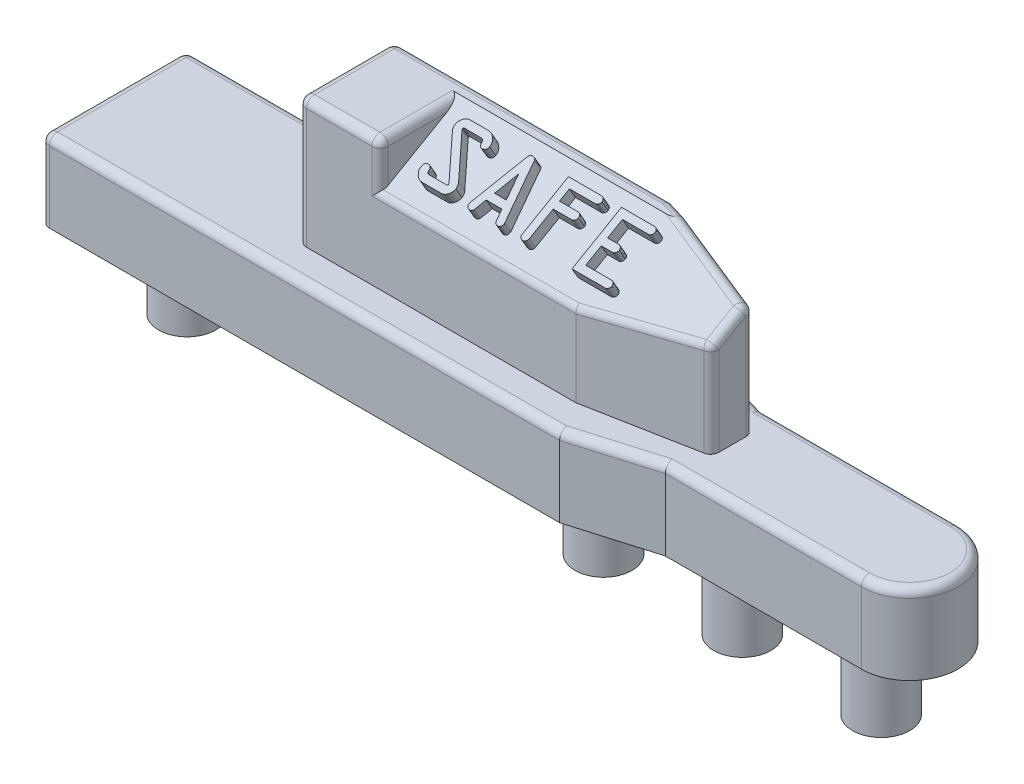
SolidWorks part; units mm, degrees
ref_plane "Front Plane" through (0, 0, 0) normal (0, 0, 1) x (1, 0, 0)
ref_plane "Top Plane" through (0, 0, 0) normal (0, 1, 0) x (1, 0, 0)
ref_plane "Right Plane" through (0, 0, 0) normal (1, 0, 0) x (0, 0, -1)
sketch "Sketch1" plane through (0, 0, 0) normal (0, 0, 1) x (1, 0, 0)
  line L1 (-17.469, 9.1211) -> (86.531, 9.1211)
  line L2 (-17.469, 9.1211) -> (-17.469, -0.5989)
  line L3 (-17.469, -0.5989) -> (86.531, -0.5989)
  line L4 (86.531, 9.1211) -> (86.531, -0.5989)
  dimension "D1" = 9.72
  dimension "D2" = 104
extrude "body" add sketch "Sketch1" along normal blind 17.75
sketch "Sketch2" plane through (0, -0.5989, 0) normal (0, -1, 0) x (1, 0, 0)
  line L7 (80.031, 17.75) -> (80.031, 0) construction
  line L8 (46.031, 17.75) -> (56.031, 14.8)
  line L9 (56.031, 14.8) -> (80.031, 14.8)
  line L10 (80.031, 2.95) -> (56.031, 2.95)
  line L11 (46.031, 0) -> (56.031, 2.95)
  line L12 (46.031, 17.75) -> (86.531, 17.75)
  line L13 (86.531, 17.75) -> (86.531, 0)
  line L14 (86.531, 0) -> (46.031, 0)
  line L15 (-17.469, 17.75) -> (86.531, 17.75) construction
  line L16 (86.531, 17.75) -> (86.531, 0) construction
  line L17 (-17.469, 17.75) -> (-17.469, 0) construction
  line L18 (-17.469, 0) -> (86.531, 0) construction
  arc A1 (80.031, 2.95) -> (80.031, 14.8) centre (80.031, 8.875) ccw
  dimension "D2" = 24
  dimension "D3" = 24
  dimension "D4" = 6.5
  dimension "D5" = 63.5
  dimension "D6" = 11.85
  dimension "D7" = 0
  dimension "D8" = 0
  dimension "D9" = 63.5
  dimension "D10" = 0
extrude "front_cut_out" cut sketch "Sketch2" against normal through all
sketch "Sketch4" plane through (0, -0.5989, 0) normal (0, -1, 0) x (1, 0, 0)
  line L0 (-17.469, 0) -> (46.031, 0) construction
  line L1 (-17.469, 17.75) -> (-17.469, 0) construction
  line L2 (-8.469, 17.75) -> (-8.469, 0) construction
  line L3 (-17.469, 17.75) -> (46.031, 17.75) construction
  line L4 (59.531, 14.8) -> (59.531, 2.95) construction
  line L5 (56.031, 14.8) -> (80.031, 14.8) construction
  line L6 (80.031, 2.95) -> (56.031, 2.95) construction
  line L7 (76.531, 14.8) -> (76.531, 2.95) construction
  circle A0 centre (-8.469, 8.875) radius 3.5
  circle A1 centre (42.531, 8.875) radius 3.5
  circle A2 centre (59.531, 8.875) radius 3.5
  circle A3 centre (76.531, 8.875) radius 3.5
  dimension "D1" = 7
  dimension "D3" = 7
  dimension "D4" = 7
  dimension "D2" = 51
  dimension "D6" = 9
  dimension "D7" = 68
  dimension "D8" = 85
extrude "Boss-Extrude2" add sketch "Sketch4" along normal blind 9.5
sketch "Sketch6" plane through (0, 9.1211, 0) normal (0, 1, 0) x (1, 0, 0)
  line L0 (10.031, -2) -> (10.031, -13.75)
  line L1 (10.031, -13.75) -> (44.031, -13.75)
  line L2 (44.031, -13.75) -> (58.031, -11.0906)
  line L3 (58.031, -11.0906) -> (58.031, -6.2)
  line L4 (10.031, -2) -> (44.031, -2)
  line L5 (44.031, -2) -> (58.031, -6.2)
  line L6 (-17.469, -17.75) -> (-17.469, 0) construction
  line L7 (46.031, -17.75) -> (-17.469, -17.75) construction
  line L8 (46.031, 0) -> (-17.469, 0) construction
  dimension "D1" = 27.5
  dimension "D2" = 4
  dimension "D3" = 2
  dimension "D4" = 2
  dimension "D5" = 2
  dimension "D6" = 2
extrude "bolt_stopper" add sketch "Sketch6" along normal blind 15.7
fillet "Fillet3" radius 1 2 edges at (-17.469, 4.2611, 0) (-17.469, 4.2611, 17.75)
fillet "Fillet4" radius 1 10 edges at (-17.1761, 9.1211, 17.4571) (-17.1761, 9.1211, 0.2929) (51.031, 9.1211, 1.475) (14.781, 9.1211, 0) (68.031, 9.1211, 2.95) (85.956, 9.1211, 8.875) (51.031, 9.1211, 16.275) (68.031, 9.1211, 14.8) (14.781, 9.1211, 17.75) (-17.469, 9.1211, 8.875)
fillet "Fillet5" radius 1 1 edges at (58.031, 24.8211, 8.6453)
ref_plane "Plane1" through (0, 19.1211, 0) normal (0, 1, 0) x (1, 0, 0)
ref_axis "Axis1" through (37.1966, 19.1211, 13.75) along (-1, 0, 0)
ref_plane "Plane2" through (0, 20.2947, 11.7172) normal (0, -0.866, -0.5) x (-1, 0, 0)
ref_axis "Axis2" through (30.049, 24.8211, 3.8773) along (-1, 0, 0)
sketch "Sketch10" plane through (0, 20.2947, 11.7172) normal (0, -0.866, -0.5) x (-1, 0, 0)
  line L1 (-20.031, 15.2992) -> (-20.031, -6.006)
  line L2 (-20.031, -6.006) -> (-65.6163, -6.006)
  line L3 (-65.6163, -6.006) -> (-65.6163, 15.2992)
  line L4 (-65.6163, 15.2992) -> (-20.031, 15.2992)
  line L5 (-10.031, 10.6785) -> (-10.031, 0.5027) construction
  dimension "D1" = 10
extrude "Cut-Extrude1" cut sketch "Sketch10" against normal through all
ref_plane "Plane3" through (0, 20.2947, 11.7172) normal (0, 0.866, 0.5) x (1, 0, 0)
sketch "Sketch12" plane through (0, 20.2947, 11.7172) normal (0, 0.866, 0.5) x (1, 0, 0)
  line L0 (21.531, 0.1527) -> (42.8389, 0.1527) construction
  line L1 (37.1966, -2.3473) -> (10.031, -2.3473) construction
  line L2 (20.031, -2.3473) -> (20.031, 9.0527) construction
  text T0 "SAFE" font "OCR A Extended" height 7
  dimension "D1" = 2.5
  dimension "D2" = 1.5
extrude "safe_text" add sketch "Sketch12" along normal blind 1.5
fillet "Fillet8" radius 1 14 edges at (10.031, 16.9711, 2) (10.031, 16.9711, 13.75) (10.031, 24.8211, 7.875) (15.031, 24.8211, 13.75) (20.031, 24.8211, 8.8137) (20.031, 21.9711, 13.75) (32.031, 19.1211, 13.75) (51.031, 19.8888, 12.4203) (58.031, 22.0683, 8.6453) (58.031, 14.8888, 11.0906) (58.031, 16.3006, 6.2) (54.1598, 24.1506, 5.0387) (47.1598, 24.8211, 2.9387) (27.031, 24.8211, 2)
